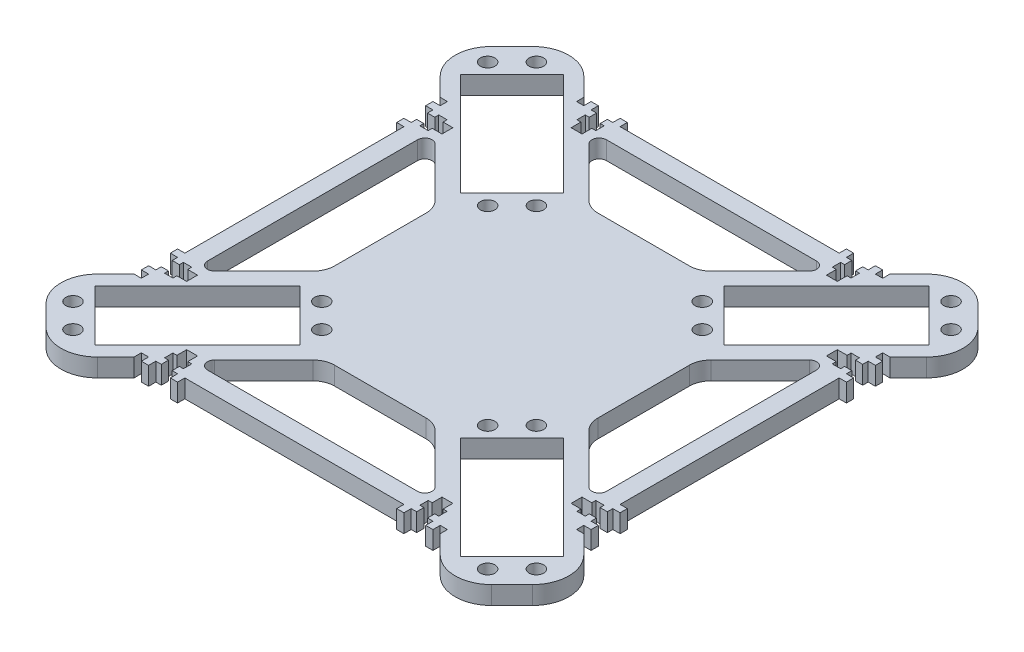
SolidWorks part; units mm, degrees
ref_plane "Front Plane" through (0, 0, 0) normal (0, 0, 1) x (1, 0, 0)
ref_plane "Top Plane" through (0, 0, 0) normal (0, 1, 0) x (1, 0, 0)
ref_plane "Right Plane" through (0, 0, 0) normal (1, 0, 0) x (0, 0, -1)
sketch "Sketch1" plane through (0, 0, 0) normal (0, 1, 0) x (1, 0, 0)
  line L1 (0, 0) -> (120, 0)
  line L2 (0, 0) -> (0, 120)
  line L3 (0, 120) -> (120, 120)
  line L4 (120, 0) -> (120, 120)
  dimension "D1" = 120
  dimension "D2" = 120
extrude "Boss-Extrude1" add sketch "Sketch1" along normal blind 5
sketch "Sketch2" plane through (0, 5, 0) normal (0, 1, 0) x (1, 0, 0)
  line L0 (60, 120) -> (60, 0) construction
  line L1 (120, 120) -> (0, 120) construction
  line L2 (0, 0) -> (120, 0) construction
  line L3 (120, 60) -> (0, 60) construction
  line L4 (120, 0) -> (120, 120) construction
  line L5 (0, 120) -> (0, 0) construction
  line L6 (60, 60) -> (120, 120) construction
  line L7 (110.1005, 110.1005) -> (120, 100.201) construction
  line L8 (110.1005, 110.1005) -> (100.201, 120) construction
  line L9 (100.201, 120) -> (120, 100.201)
  line L10 (100.201, 120) -> (114.3431, 134.1421)
  line L11 (120, 100.201) -> (134.1421, 114.3431)
  line L12 (114.3431, 134.1421) -> (134.1421, 114.3431)
  line L13 (0, 100.201) -> (-14.1421, 114.3431)
  line L14 (5.6569, 134.1421) -> (-14.1421, 114.3431)
  line L15 (19.799, 120) -> (5.6569, 134.1421)
  line L16 (19.799, 120) -> (0, 100.201)
  line L17 (19.799, 0) -> (0, 19.799)
  line L18 (19.799, 0) -> (5.6569, -14.1421)
  line L19 (5.6569, -14.1421) -> (-14.1421, 5.6569)
  line L20 (0, 19.799) -> (-14.1421, 5.6569)
  line L21 (120, 19.799) -> (134.1421, 5.6569)
  line L22 (114.3431, -14.1421) -> (134.1421, 5.6569)
  line L23 (100.201, 0) -> (114.3431, -14.1421)
  line L24 (100.201, 0) -> (120, 19.799)
  point P33 (120, 100.201)
  point P34 (100.201, 120)
  dimension "D1" = 28
  dimension "D2" = 20
extrude "Boss-Extrude3" add sketch "Sketch2" against normal blind 5
sketch "Sketch3" plane through (0, 5, 0) normal (0, 1, 0) x (1, 0, 0)
  line L0 (-4.2426, -4.2426) -> (124.2426, 124.2426) construction
  line L1 (-14.1421, 5.6569) -> (5.6569, -14.1421) construction
  line L2 (134.1421, 114.3431) -> (114.3431, 134.1421) construction
  line L3 (0, 19.799) -> (19.799, 0) construction
  line L4 (2.4819, 2.4819) -> (12.3814, -7.4176) construction
  line L5 (5.6569, -14.1421) -> (19.799, 0) construction
  line L6 (30.7662, 30.7662) -> (43.5292, 18.0033) construction
  line L7 (9.553, -4.5891) -> (37.8373, 23.6951)
  line L8 (9.553, -4.5891) -> (-4.5891, 9.553)
  line L9 (37.8373, 23.6951) -> (23.6951, 37.8373)
  line L10 (-4.5891, 9.553) -> (23.6951, 37.8373)
  line L11 (-0.5233, -0.5233) -> (6.5401, -7.5867) construction
  line L12 (23.6951, 9.553) -> (9.553, 23.6951) construction
  line L13 (0, 60) -> (120, 60) construction
  line L14 (0, 100.201) -> (0, 19.799) construction
  line L15 (120, 19.799) -> (120, 100.201) construction
  line L16 (60, 0) -> (60, 120) construction
  line L17 (19.799, 0) -> (100.201, 0) construction
  line L18 (100.201, 120) -> (19.799, 120) construction
  line L19 (82.1627, 23.6951) -> (96.3049, 37.8373)
  line L20 (124.5891, 9.553) -> (96.3049, 37.8373)
  line L21 (110.447, -4.5891) -> (124.5891, 9.553)
  line L22 (110.447, -4.5891) -> (82.1627, 23.6951)
  line L23 (110.447, 124.5891) -> (82.1627, 96.3049)
  line L24 (110.447, 124.5891) -> (124.5891, 110.447)
  line L25 (124.5891, 110.447) -> (96.3049, 82.1627)
  line L26 (82.1627, 96.3049) -> (96.3049, 82.1627)
  line L27 (37.8373, 96.3049) -> (23.6951, 82.1627)
  line L28 (-4.5891, 110.447) -> (23.6951, 82.1627)
  line L29 (9.553, 124.5891) -> (-4.5891, 110.447)
  line L30 (9.553, 124.5891) -> (37.8373, 96.3049)
  circle A0 centre (2.8355, -3.882) radius 2
  circle A1 centre (-3.882, 2.8355) radius 2
  circle A2 centre (37.1302, 30.4127) radius 2
  circle A3 centre (30.4127, 37.1302) radius 2
  circle A4 centre (117.1645, -3.882) radius 2
  circle A5 centre (123.882, 2.8355) radius 2
  circle A6 centre (82.8698, 30.4127) radius 2
  circle A7 centre (89.5873, 37.1302) radius 2
  circle A8 centre (117.1645, 123.882) radius 2
  circle A9 centre (123.882, 117.1645) radius 2
  circle A10 centre (82.8698, 89.5873) radius 2
  circle A11 centre (89.5873, 82.8698) radius 2
  circle A12 centre (2.8355, 123.882) radius 2
  circle A13 centre (-3.882, 117.1645) radius 2
  circle A14 centre (37.1302, 89.5873) radius 2
  circle A15 centre (30.4127, 82.8698) radius 2
  point P10 (9.8995, 9.8995)
  point P11 (30.7662, 30.7662)
  point P13 (2.4819, 2.4819)
  dimension "D5" = 4
  dimension "D6" = 9.5
  dimension "D7" = 4.25
  dimension "D1" = 29.51
  dimension "D2" = 10.49
  dimension "D3" = 20
  dimension "D4" = 4.25
extrude "Cut-Extrude1" cut sketch "Sketch3" against normal blind 5
sketch "Sketch5" plane through (0, 5, 0) normal (0, 1, 0) x (1, 0, 0)
  line L0 (60, 0) -> (60, 120) construction
  line L1 (19.799, 0) -> (100.201, 0) construction
  line L2 (100.201, 120) -> (19.799, 120) construction
  line L3 (60, 15) -> (65, 15) construction
  line L4 (65, 15) -> (60, 10)
  line L5 (65, 15) -> (60, 5)
  line L6 (55, 15) -> (60, 5)
  line L7 (55, 15) -> (60, 10)
  dimension "D1" = 5
  dimension "D2" = 5
  dimension "D3" = 10
  dimension "D4" = 5
extrude "Cut-Extrude3" cut sketch "Sketch5" against normal blind 5
sketch "Sketch6" plane through (0, 5, 0) normal (0, 1, 0) x (1, 0, 0)
  line L0 (0, 19.799) -> (0, 17.799)
  line L1 (0, 17.799) -> (-2, 17.799)
  line L2 (0, 19.799) -> (-14.1421, 5.6569) construction
  line L3 (-2, 17.799) -> (0, 19.799)
  line L4 (0, 0) -> (124.2426, 124.2426) construction
  line L5 (134.1421, 114.3431) -> (114.3431, 134.1421) construction
  line L6 (60, 120) -> (60, 0) construction
  line L7 (100.201, 120) -> (19.799, 120) construction
  line L8 (19.799, 0) -> (100.201, 0) construction
  line L9 (0, 60) -> (120, 60) construction
  line L10 (0, 100.201) -> (0, 19.799) construction
  line L11 (120, 19.799) -> (120, 100.201) construction
  line L12 (17.799, -2) -> (19.799, 0)
  line L13 (17.799, 0) -> (17.799, -2)
  line L14 (19.799, 0) -> (17.799, 0)
  line L15 (100.201, 0) -> (102.201, 0)
  line L16 (102.201, 0) -> (102.201, -2)
  line L17 (102.201, -2) -> (100.201, 0)
  line L18 (122, 17.799) -> (120, 19.799)
  line L19 (120, 17.799) -> (122, 17.799)
  line L20 (120, 19.799) -> (120, 17.799)
  line L21 (120, 100.201) -> (120, 102.201)
  line L22 (120, 102.201) -> (122, 102.201)
  line L23 (122, 102.201) -> (120, 100.201)
  line L24 (102.201, 122) -> (100.201, 120)
  line L25 (102.201, 120) -> (102.201, 122)
  line L26 (100.201, 120) -> (102.201, 120)
  line L27 (19.799, 120) -> (17.799, 120)
  line L28 (17.799, 120) -> (17.799, 122)
  line L29 (17.799, 122) -> (19.799, 120)
  line L30 (-2, 102.201) -> (0, 100.201)
  line L31 (0, 102.201) -> (-2, 102.201)
  line L32 (0, 100.201) -> (0, 102.201)
  dimension "D1" = 2
extrude "Cut-Extrude4" cut sketch "Sketch6" against normal blind 10
fillet "Fillet1" radius 10 8 edges at (5.6569, 2.5, 14.1421) (-14.1421, 2.5, -5.6569) (-14.1421, 2.5, -114.3431) (5.6569, 2.5, -134.1421) (114.3431, 2.5, -134.1421) (134.1421, 2.5, -114.3431) (134.1421, 2.5, -5.6569) (114.3431, 2.5, 14.1421)
sketch "Sketch7" plane through (0, 5, 0) normal (0, 1, 0) x (1, 0, 0)
  line L0 (0, 60) -> (120, 60) construction
  line L1 (0, 102.201) -> (0, 17.799) construction
  line L2 (120, 17.799) -> (120, 102.201) construction
  line L3 (60, 120) -> (60, 0) construction
  line L4 (102.201, 120) -> (17.799, 120) construction
  line L5 (17.799, 0) -> (102.201, 0) construction
  line L6 (23.6951, 37.8373) -> (23.6951, 82.1627) construction
  line L7 (23.6951, 44.9084) -> (23.6951, 75.0916)
  line L8 (23.6951, 75.0916) -> (5, 93.7868)
  line L9 (5, 93.7868) -> (5, 26.2132)
  line L10 (96.3049, 44.9084) -> (115, 26.2132)
  line L11 (-4.5891, 110.447) -> (23.6951, 82.1627) construction
  line L12 (23.6951, 44.9084) -> (5, 26.2132)
  line L13 (115, 93.7868) -> (115, 26.2132)
  line L14 (96.3049, 75.0916) -> (115, 93.7868)
  line L15 (96.3049, 44.9084) -> (96.3049, 75.0916)
  line L16 (60, 60) -> (89.2338, 89.2338) construction
  line L17 (82.1627, 96.3049) -> (96.3049, 82.1627) construction
  line L18 (75.0916, 96.3049) -> (93.7868, 115)
  line L19 (93.7868, 115) -> (26.2132, 115)
  line L20 (44.9083, 96.3049) -> (26.2132, 115)
  line L21 (44.9083, 96.3049) -> (75.0916, 96.3049)
  line L22 (44.9084, 23.6951) -> (26.2132, 5)
  line L23 (93.7868, 5) -> (26.2132, 5)
  line L24 (75.0917, 23.6951) -> (93.7868, 5)
  line L25 (44.9084, 23.6951) -> (75.0917, 23.6951)
  point P16 (23.6951, 60)
  point P24 (23.6951, 60)
  point P25 (5, 60)
  point P29 (115, 60)
  point P30 (96.3049, 60)
  point P43 (60, 5)
  point P44 (60, 23.6951)
  dimension "D1" = 5
  dimension "D2" = 5
extrude "Cut-Extrude5" cut sketch "Sketch7" against normal blind 10
fillet "Fillet2" radius 2 8 edges at (115, 2.5, -26.2132) (115, 2.5, -93.7868) (93.7868, 2.5, -115) (26.2132, 2.5, -115) (26.2132, 2.5, -5) (93.7868, 2.5, -5) (5, 2.5, -26.2132) (5, 2.5, -93.7868)
fillet "Fillet3" radius 6 8 edges at (44.9083, 2.5, -96.3049) (75.0916, 2.5, -96.3049) (23.6951, 2.5, -75.0916) (23.6951, 2.5, -44.9084) (75.0917, 2.5, -23.6951) (44.9084, 2.5, -23.6951) (96.3049, 2.5, -44.9084) (96.3049, 2.5, -75.0916)
sketch "Sketch8" plane through (0, 5, 0) normal (0, 1, 0) x (1, 0, 0)
  line L0 (60, 0) -> (60, 120) construction
  line L1 (17.799, 0) -> (102.201, 0) construction
  line L2 (102.201, 120) -> (17.799, 120) construction
  line L3 (0, 60) -> (120, 60) construction
  line L4 (0, 102.201) -> (0, 17.799) construction
  line L5 (120, 17.799) -> (120, 102.201) construction
  line L6 (-4.2426, 124.2426) -> (124.2426, -4.2426) construction
  line L7 (-1.4142, 127.0711) -> (-7.0711, 121.4142) construction
  line L8 (121.4142, -7.0711) -> (127.0711, -1.4142) construction
  line L9 (24.799, 0) -> (24.799, 7) construction
  line L10 (23.299, 2) -> (23.299, 0)
  line L11 (26.299, 7) -> (23.299, 7)
  line L12 (26.299, 7) -> (26.299, 4.3)
  line L13 (26.299, 0) -> (23.299, 0)
  line L14 (23.299, 7) -> (23.299, 4.3)
  line L15 (26.299, 7) -> (23.299, 0) construction
  line L16 (26.299, 0) -> (23.299, 7) construction
  line L17 (23.299, 2) -> (22.199, 2)
  line L19 (23.299, 4.3) -> (22.199, 4.3)
  line L20 (22.199, 2) -> (22.199, 4.3)
  line L21 (26.299, 4.3) -> (27.399, 4.3)
  line L22 (27.399, 2) -> (27.399, 4.3)
  line L23 (26.299, 2) -> (27.399, 2)
  line L24 (26.299, 2) -> (26.299, 0)
  line L25 (17.799, 0) -> (17.799, -2) construction
  line L26 (93.701, 0) -> (96.701, 7) construction
  line L27 (93.701, 7) -> (96.701, 0) construction
  line L28 (95.201, 0) -> (95.201, 7) construction
  line L29 (93.701, 2) -> (93.701, 0)
  line L30 (93.701, 2) -> (92.601, 2)
  line L31 (92.601, 2) -> (92.601, 4.3)
  line L32 (93.701, 4.3) -> (92.601, 4.3)
  line L33 (97.801, 2) -> (97.801, 4.3)
  line L34 (96.701, 4.3) -> (97.801, 4.3)
  line L35 (96.701, 2) -> (97.801, 2)
  line L36 (96.701, 7) -> (96.701, 4.3)
  line L37 (93.701, 0) -> (96.701, 0)
  line L38 (93.701, 7) -> (93.701, 4.3)
  line L39 (93.701, 7) -> (96.701, 7)
  line L40 (96.701, 2) -> (96.701, 0)
  line L41 (95.201, 120) -> (95.201, 113) construction
  line L42 (93.701, 113) -> (96.701, 120) construction
  line L43 (93.701, 120) -> (96.701, 113) construction
  line L44 (26.299, 120) -> (23.299, 113) construction
  line L45 (26.299, 113) -> (23.299, 120) construction
  line L46 (24.799, 120) -> (24.799, 113) construction
  line L47 (96.701, 118) -> (96.701, 120)
  line L48 (93.701, 113) -> (96.701, 113)
  line L49 (93.701, 113) -> (93.701, 115.7)
  line L50 (93.701, 120) -> (96.701, 120)
  line L51 (96.701, 113) -> (96.701, 115.7)
  line L52 (96.701, 118) -> (97.801, 118)
  line L53 (96.701, 115.7) -> (97.801, 115.7)
  line L54 (97.801, 118) -> (97.801, 115.7)
  line L55 (93.701, 115.7) -> (92.601, 115.7)
  line L56 (92.601, 118) -> (92.601, 115.7)
  line L57 (93.701, 118) -> (92.601, 118)
  line L58 (93.701, 118) -> (93.701, 120)
  line L59 (26.299, 118) -> (26.299, 120)
  line L60 (26.299, 118) -> (27.399, 118)
  line L61 (27.399, 118) -> (27.399, 115.7)
  line L62 (26.299, 115.7) -> (27.399, 115.7)
  line L63 (22.199, 118) -> (22.199, 115.7)
  line L64 (23.299, 115.7) -> (22.199, 115.7)
  line L65 (23.299, 118) -> (22.199, 118)
  line L66 (23.299, 113) -> (23.299, 115.7)
  line L67 (26.299, 120) -> (23.299, 120)
  line L68 (26.299, 113) -> (26.299, 115.7)
  line L69 (26.299, 113) -> (23.299, 113)
  line L70 (23.299, 118) -> (23.299, 120)
  line L71 (0, 95.201) -> (7, 95.201) construction
  line L72 (7, 93.701) -> (0, 96.701) construction
  line L73 (0, 93.701) -> (7, 96.701) construction
  line L74 (0, 26.299) -> (7, 23.299) construction
  line L75 (7, 26.299) -> (0, 23.299) construction
  line L76 (0, 24.799) -> (7, 24.799) construction
  line L77 (120, 24.799) -> (113, 24.799) construction
  line L78 (113, 26.299) -> (120, 23.299) construction
  line L79 (120, 26.299) -> (113, 23.299) construction
  line L80 (120, 93.701) -> (113, 96.701) construction
  line L81 (113, 93.701) -> (120, 96.701) construction
  line L82 (120, 95.201) -> (113, 95.201) construction
  line L83 (2, 96.701) -> (0, 96.701)
  line L84 (7, 93.701) -> (7, 96.701)
  line L85 (7, 93.701) -> (4.3, 93.701)
  line L86 (0, 93.701) -> (0, 96.701)
  line L87 (7, 96.701) -> (4.3, 96.701)
  line L88 (2, 96.701) -> (2, 97.801)
  line L89 (4.3, 96.701) -> (4.3, 97.801)
  line L90 (2, 97.801) -> (4.3, 97.801)
  line L91 (4.3, 93.701) -> (4.3, 92.601)
  line L92 (2, 92.601) -> (4.3, 92.601)
  line L93 (2, 93.701) -> (2, 92.601)
  line L94 (2, 93.701) -> (0, 93.701)
  line L95 (2, 26.299) -> (0, 26.299)
  line L96 (2, 26.299) -> (2, 27.399)
  line L97 (2, 27.399) -> (4.3, 27.399)
  line L98 (4.3, 26.299) -> (4.3, 27.399)
  line L99 (2, 22.199) -> (4.3, 22.199)
  line L100 (4.3, 23.299) -> (4.3, 22.199)
  line L101 (2, 23.299) -> (2, 22.199)
  line L102 (7, 23.299) -> (4.3, 23.299)
  line L103 (0, 26.299) -> (0, 23.299)
  line L104 (7, 26.299) -> (4.3, 26.299)
  line L105 (7, 26.299) -> (7, 23.299)
  line L106 (2, 23.299) -> (0, 23.299)
  line L107 (118, 23.299) -> (120, 23.299)
  line L108 (113, 26.299) -> (113, 23.299)
  line L109 (113, 26.299) -> (115.7, 26.299)
  line L110 (120, 26.299) -> (120, 23.299)
  line L111 (113, 23.299) -> (115.7, 23.299)
  line L112 (118, 23.299) -> (118, 22.199)
  line L113 (115.7, 23.299) -> (115.7, 22.199)
  line L114 (118, 22.199) -> (115.7, 22.199)
  line L115 (115.7, 26.299) -> (115.7, 27.399)
  line L116 (118, 27.399) -> (115.7, 27.399)
  line L117 (118, 26.299) -> (118, 27.399)
  line L118 (118, 26.299) -> (120, 26.299)
  line L119 (118, 93.701) -> (120, 93.701)
  line L120 (118, 93.701) -> (118, 92.601)
  line L121 (118, 92.601) -> (115.7, 92.601)
  line L122 (115.7, 93.701) -> (115.7, 92.601)
  line L123 (118, 97.801) -> (115.7, 97.801)
  line L124 (115.7, 96.701) -> (115.7, 97.801)
  line L125 (118, 96.701) -> (118, 97.801)
  line L126 (113, 96.701) -> (115.7, 96.701)
  line L127 (120, 93.701) -> (120, 96.701)
  line L128 (113, 93.701) -> (115.7, 93.701)
  line L129 (113, 93.701) -> (113, 96.701)
  line L130 (118, 96.701) -> (120, 96.701)
  point P20 (24.799, 3.5)
  point P49 (95.201, 3.5)
  point P78 (95.201, 116.5)
  point P79 (24.799, 116.5)
  point P136 (3.5, 95.201)
  point P137 (3.5, 24.799)
  point P138 (116.5, 24.799)
  point P139 (116.5, 95.201)
  dimension "D1" = 2
  dimension "D2" = 2.3
  dimension "D3" = 7
  dimension "D4" = 7
  dimension "D5" = 3
  dimension "D6" = 1.1
extrude "Cut-Extrude6" cut sketch "Sketch8" against normal blind 10
sketch "Sketch9" plane through (0, 5, 0) normal (0, 1, 0) x (1, 0, 0)
  line L0 (7, 95.201) -> (-3.557, 95.201) construction
  line L1 (7, 93.701) -> (7, 96.701) construction
  line L2 (-4.2426, 124.2426) -> (124.2426, -4.2426) construction
  line L3 (-1.4142, 127.0711) -> (-7.0711, 121.4142) construction
  line L4 (121.4142, -7.0711) -> (127.0711, -1.4142) construction
  line L5 (60, 0) -> (60, 120) construction
  line L6 (26.299, 0) -> (93.701, 0) construction
  line L7 (93.701, 120) -> (26.299, 120) construction
  line L8 (0, 60) -> (120, 60) construction
  line L9 (0, 93.701) -> (0, 26.299) construction
  line L10 (120, 26.299) -> (120, 93.701) construction
  line L11 (0, 102.201) -> (0, 96.701) construction
  line L12 (0, 98.201) -> (-2, 98.201)
  line L13 (0, 98.201) -> (0, 100.201)
  line L14 (0, 100.201) -> (-2, 100.201)
  line L15 (-2, 98.201) -> (-2, 100.201)
  line L16 (0, 90.201) -> (-2, 90.201)
  line L17 (-2, 92.201) -> (-2, 90.201)
  line L18 (0, 92.201) -> (-2, 92.201)
  line L19 (0, 92.201) -> (0, 90.201)
  line L20 (19.799, 120) -> (19.799, 122)
  line L21 (21.799, 122) -> (19.799, 122)
  line L22 (21.799, 120) -> (21.799, 122)
  line L23 (21.799, 120) -> (19.799, 120)
  line L24 (27.799, 120) -> (29.799, 120)
  line L25 (27.799, 120) -> (27.799, 122)
  line L26 (27.799, 122) -> (29.799, 122)
  line L27 (29.799, 120) -> (29.799, 122)
  line L28 (92.201, 120) -> (92.201, 122)
  line L29 (92.201, 122) -> (90.201, 122)
  line L30 (90.201, 120) -> (90.201, 122)
  line L31 (92.201, 120) -> (90.201, 120)
  line L32 (98.201, 120) -> (100.201, 120)
  line L33 (98.201, 120) -> (98.201, 122)
  line L34 (98.201, 122) -> (100.201, 122)
  line L35 (100.201, 120) -> (100.201, 122)
  line L36 (120, 100.201) -> (122, 100.201)
  line L37 (122, 98.201) -> (122, 100.201)
  line L38 (120, 98.201) -> (122, 98.201)
  line L39 (120, 98.201) -> (120, 100.201)
  line L40 (120, 92.201) -> (120, 90.201)
  line L41 (120, 92.201) -> (122, 92.201)
  line L42 (122, 92.201) -> (122, 90.201)
  line L43 (120, 90.201) -> (122, 90.201)
  line L44 (120, 27.799) -> (122, 27.799)
  line L45 (122, 27.799) -> (122, 29.799)
  line L46 (120, 29.799) -> (122, 29.799)
  line L47 (120, 27.799) -> (120, 29.799)
  line L48 (120, 21.799) -> (120, 19.799)
  line L49 (120, 21.799) -> (122, 21.799)
  line L50 (122, 21.799) -> (122, 19.799)
  line L51 (120, 19.799) -> (122, 19.799)
  line L52 (98.201, 0) -> (98.201, -2)
  line L53 (98.201, -2) -> (100.201, -2)
  line L54 (100.201, 0) -> (100.201, -2)
  line L55 (98.201, 0) -> (100.201, 0)
  line L56 (92.201, 0) -> (90.201, 0)
  line L57 (90.201, 0) -> (90.201, -2)
  line L58 (92.201, -2) -> (90.201, -2)
  line L59 (92.201, 0) -> (92.201, -2)
  line L60 (27.799, 0) -> (27.799, -2)
  line L61 (27.799, -2) -> (29.799, -2)
  line L62 (29.799, 0) -> (29.799, -2)
  line L63 (27.799, 0) -> (29.799, 0)
  line L64 (21.799, 0) -> (19.799, 0)
  line L65 (21.799, 0) -> (21.799, -2)
  line L66 (21.799, -2) -> (19.799, -2)
  line L67 (19.799, 0) -> (19.799, -2)
  line L68 (0, 19.799) -> (-2, 19.799)
  line L69 (-2, 21.799) -> (-2, 19.799)
  line L70 (0, 21.799) -> (-2, 21.799)
  line L71 (0, 21.799) -> (0, 19.799)
  line L72 (0, 27.799) -> (0, 29.799)
  line L73 (0, 27.799) -> (-2, 27.799)
  line L74 (-2, 27.799) -> (-2, 29.799)
  line L75 (0, 29.799) -> (-2, 29.799)
  dimension "D1" = 2
  dimension "D2" = 2
  dimension "D3" = 3
extrude "Boss-Extrude4" add sketch "Sketch9" against normal blind 5
